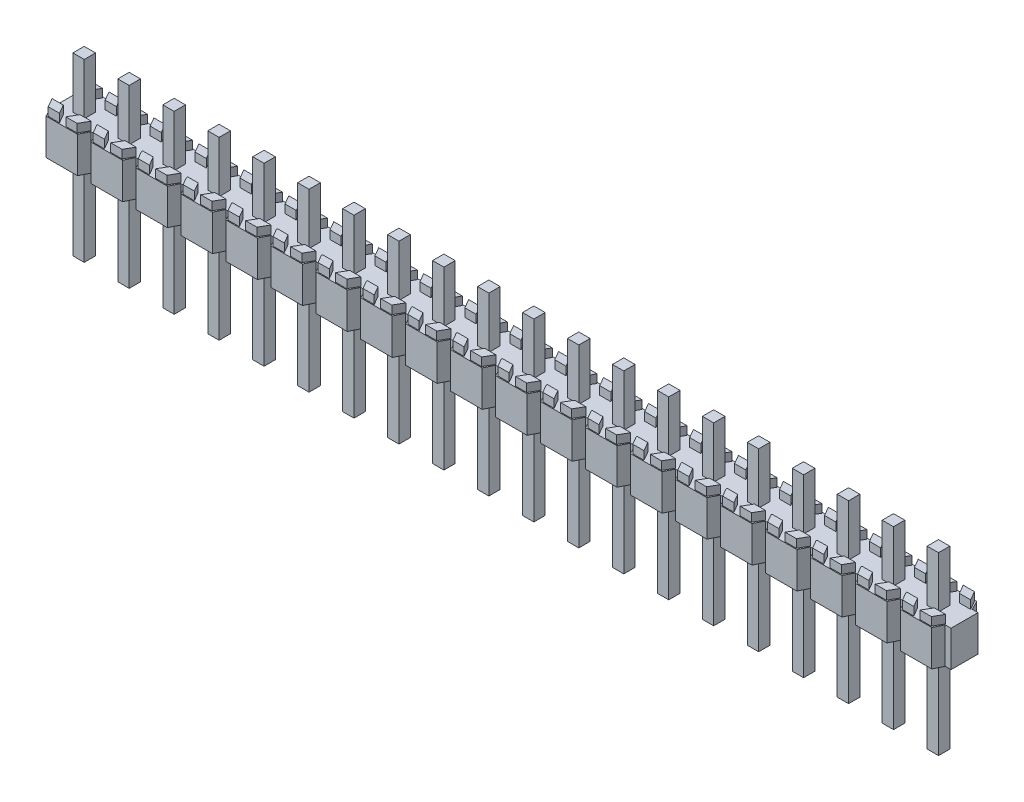
SolidWorks part; units mm, degrees
ref_plane "Front Plane" through (0, 0, 0) normal (0, 0, 1) x (1, 0, 0)
ref_plane "Top Plane" through (0, 0, 0) normal (0, 1, 0) x (1, 0, 0)
ref_plane "Right Plane" through (0, 0, 0) normal (1, 0, 0) x (0, 0, -1)
sketch "Sketch1" plane through (0, 0, 0) normal (0, 1, 0) x (1, 0, 0)
  line L0 (0, 1.5791) -> (0, -1.5527) construction
  line L2 (-0.32, 0.32) -> (0.32, 0.32)
  line L3 (-0.32, 0.32) -> (-0.32, -0.32)
  line L4 (-0.32, -0.32) -> (0.32, -0.32)
  line L5 (0.32, 0.32) -> (0.32, -0.32)
  line L6 (-0.32, 0.32) -> (0.32, -0.32) construction
  line L7 (-0.32, -0.32) -> (0.32, 0.32) construction
  line L8 (-1.143, 0.762) -> (-0.889, 1.27)
  line L9 (-0.889, 1.27) -> (0.889, 1.27)
  line L10 (0.889, 1.27) -> (1.143, 0.762)
  line L11 (1.143, 0.762) -> (1.47, 0.762)
  line L12 (1.47, 0.762) -> (1.47, -0.762)
  line L13 (1.47, -0.762) -> (1.143, -0.762)
  line L14 (1.143, -0.762) -> (0.889, -1.27)
  line L15 (0.889, -1.27) -> (-0.889, -1.27)
  line L16 (-0.889, -1.27) -> (-1.143, -0.762)
  line L17 (-1.143, -0.762) -> (-1.143, 0.762)
  line L18 (-1.7519, 0.762) -> (1.5375, 0.762) construction
  line L19 (1.0554, 0) -> (-1.5628, 0) construction
  line L20 (-1.697, -0.762) -> (2.4529, -0.762) construction
  point P3 (0, 0)
  dimension "D1" = 0.64
  dimension "D2" = 0.64
  dimension "D3" = 0.889
  dimension "D4" = 1.778
  dimension "D5" = 1.27
  dimension "D6" = 1.143
  dimension "D7" = 0.762
  dimension "D8" = 1.47
extrude "Boss-Extrude1" add sketch "Sketch1" along normal blind 1.48 and the other way blind 1.02
sketch "Sketch2" plane through (0, 1.48, 0) normal (0, 1, 0) x (1, 0, 0)
  line L0 (-1.1061, -0.7112) -> (-0.4711, -0.7112)
  line L1 (-0.4711, -0.7112) -> (-0.1778, -1.2192)
  line L2 (-0.1778, -1.2192) -> (-0.8128, -1.2192)
  line L3 (-1.143, 0.762) -> (-1.143, -0.762) construction
  line L4 (-0.889, 1.27) -> (-1.143, 0.762) construction
  line L5 (-0.8128, -1.2192) -> (-1.1061, -0.7112)
  line L6 (0, 1.3694) -> (0, -1.4569) construction
  line L7 (-1.5186, 0) -> (1.896, 0) construction
  line L8 (-0.8128, 1.2192) -> (-1.1061, 0.7112)
  line L9 (-0.1778, 1.2192) -> (-0.8128, 1.2192)
  line L10 (-0.4711, 0.7112) -> (-0.1778, 1.2192)
  line L11 (-1.1061, 0.7112) -> (-0.4711, 0.7112)
  line L12 (1.1061, 0.7112) -> (0.4711, 0.7112)
  line L13 (0.4711, 0.7112) -> (0.1778, 1.2192)
  line L14 (0.1778, 1.2192) -> (0.8128, 1.2192)
  line L15 (0.8128, 1.2192) -> (1.1061, 0.7112)
  line L16 (0.8128, -1.2192) -> (1.1061, -0.7112)
  line L17 (0.1778, -1.2192) -> (0.8128, -1.2192)
  line L18 (0.4711, -0.7112) -> (0.1778, -1.2192)
  line L19 (1.1061, -0.7112) -> (0.4711, -0.7112)
  line L20 (0.889, 1.27) -> (-0.889, 1.27) construction
  line L21 (1.143, 0.762) -> (0.889, 1.27) construction
  line L22 (1.47, 0.762) -> (1.143, 0.762) construction
  line L23 (1.47, -0.762) -> (1.47, 0.762) construction
  line L24 (1.143, -0.762) -> (1.47, -0.762) construction
  line L25 (0.889, -1.27) -> (1.143, -0.762) construction
  line L26 (-0.889, -1.27) -> (0.889, -1.27) construction
  line L27 (-1.143, -0.762) -> (-0.889, -1.27) construction
  line L28 (-1.143, 0.762) -> (-1.143, -0.762)
  line L29 (-0.889, 1.27) -> (-1.143, 0.762)
  line L30 (0.889, 1.27) -> (-0.889, 1.27)
  line L31 (1.143, 0.762) -> (0.889, 1.27)
  line L32 (1.47, 0.762) -> (1.143, 0.762)
  line L33 (1.47, -0.762) -> (1.47, 0.762)
  line L34 (1.143, -0.762) -> (1.47, -0.762)
  line L35 (0.889, -1.27) -> (1.143, -0.762)
  line L36 (-0.889, -1.27) -> (0.889, -1.27)
  line L37 (-1.143, -0.762) -> (-0.889, -1.27)
extrude "Cut-Extrude2" cut sketch "Sketch2" against normal blind 0.47
sketch "Sketch3" plane through (0, 1.01, 0) normal (0, 1, 0) x (1, 0, 0)
  line L4 (-0.32, 0.32) -> (0.32, 0.32)
  line L5 (0.32, 0.32) -> (0.32, -0.32)
  line L6 (0.32, -0.32) -> (-0.32, -0.32)
  line L7 (-0.32, -0.32) -> (-0.32, 0.32)
extrude "Boss-Extrude2" add sketch "Sketch3" along normal blind 2.9 separate body
sketch "Sketch4" plane through (0, -1.02, 0) normal (0, -1, 0) x (1, 0, 0)
  line L4 (-0.32, -0.32) -> (0.32, -0.32)
  line L5 (0.32, -0.32) -> (0.32, 0.32)
  line L6 (0.32, 0.32) -> (-0.32, 0.32)
  line L7 (-0.32, 0.32) -> (-0.32, -0.32)
  line L8 (-0.32, -0.32) -> (0.32, -0.32)
  line L9 (0.32, -0.32) -> (0.32, 0.32)
  line L10 (0.32, 0.32) -> (-0.32, 0.32)
  line L11 (-0.32, 0.32) -> (-0.32, -0.32)
  dimension "D1" = 0
extrude "Boss-Extrude3" add sketch "Sketch4" along normal blind 5 separate body
pattern_linear "LPattern1" count 20 spacing 2.54 along (1, 0, 0) of "Boss-Extrude1", "Cut-Extrude2", "Boss-Extrude2", "Boss-Extrude3"
